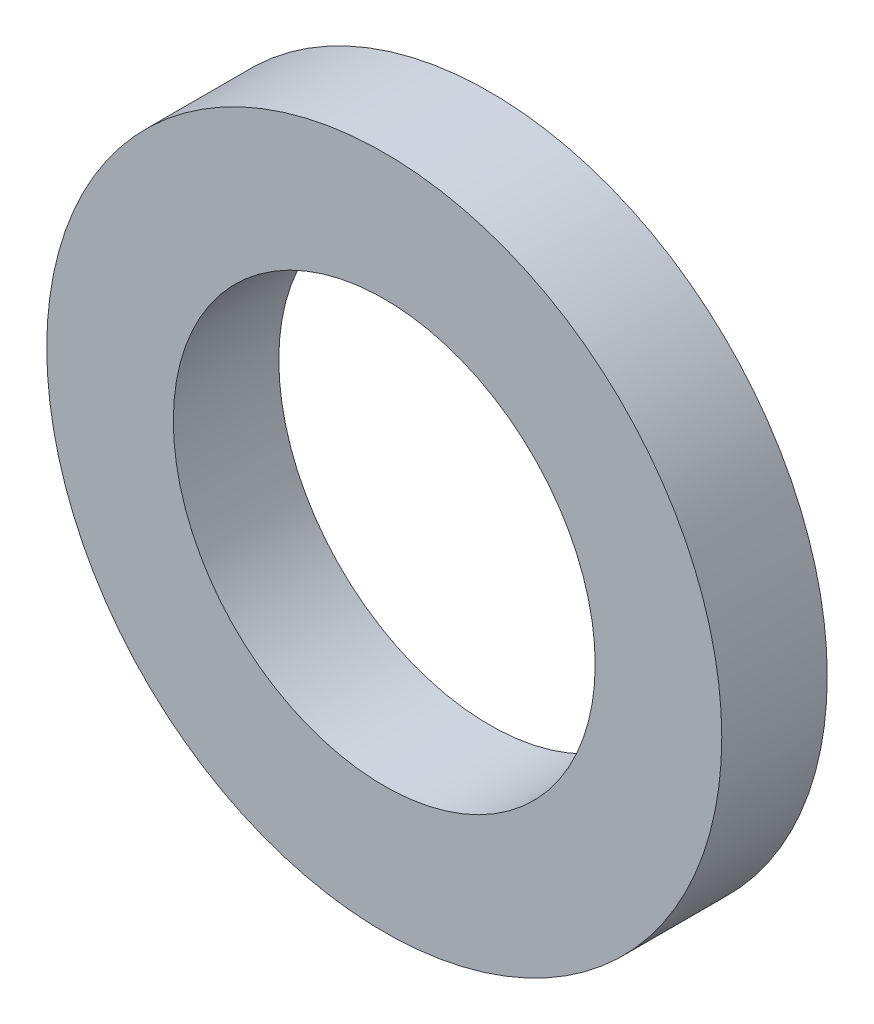
SolidWorks part; units mm, degrees
ref_plane "Front Plane" through (0, 0, 0) normal (0, 0, 1) x (1, 0, 0)
ref_plane "Top Plane" through (0, 0, 0) normal (0, 1, 0) x (1, 0, 0)
ref_plane "Right Plane" through (0, 0, 0) normal (1, 0, 0) x (0, 0, -1)
sketch "Sketch1" plane through (0, 0, 0) normal (0, 0, 1) x (1, 0, 0)
  circle A0 centre (0, 0) radius 12.7
  circle A1 centre (0, 0) radius 7.9375
  dimension "D1" = 15.875
  dimension "D2" = 25.4
extrude "Boss-Extrude1" add sketch "Sketch1" along normal blind 3.9688
scale "Scale1" scale about centroid uniform scaling yes scale factor 0.75
